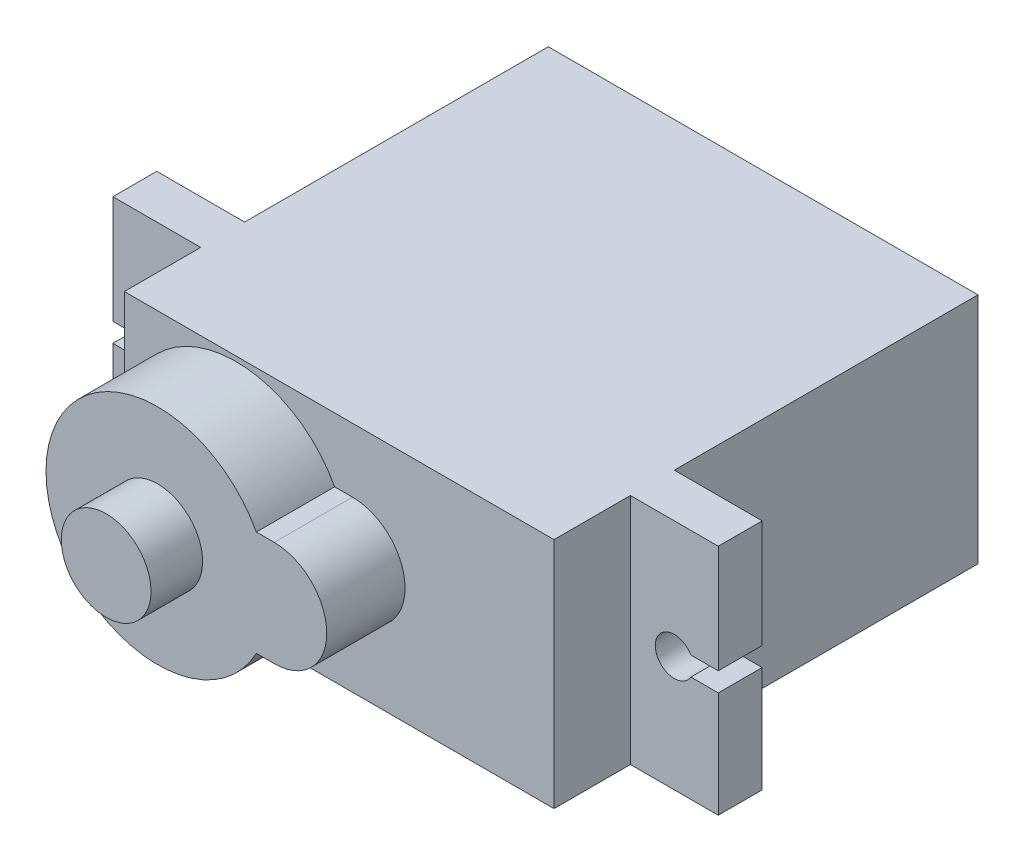
SolidWorks part; units mm, degrees
note: '?' marks a value the reader was unsure of.
ref_plane "Płaszczyzna przednia" through (0, 0, 0) normal (0, 0, 1) x (1, 0, 0)
ref_plane "Płaszczyzna górna" through (0, 0, 0) normal (0, 1, 0) x (1, 0, 0)
ref_plane "Płaszczyzna prawa" through (0, 0, 0) normal (1, 0, 0) x (0, 0, -1)
sketch "Szkic1" plane through (0, 0, 0) normal (0, 0, 1) x (1, 0, 0)
  line L1 (-22.7209, -0.2755) -> (-0.2209, -0.2755)
  line L2 (-22.7209, -0.2755) -> (-22.7209, -12.4755)
  line L3 (-22.7209, -12.4755) -> (-0.2209, -12.4755)
  line L4 (-0.2209, -0.2755) -> (-0.2209, -12.4755)
  dimension "D1" = 22.5
  dimension "D2" = 12.2
  dimension "D3" = 0.2209
  dimension "D4" = 0.2755
extrude "Dodanie-wyciągnięcie1" add sketch "Szkic1" along normal blind 22.2
sketch "Szkic2" plane through (-0.2209, 0, 0) normal (1, 0, 0) x (0, 0, -1)
  line L1 (-18.2, -12.4755) -> (-15.9, -12.4755)
  line L2 (-18.2, -12.4755) -> (-18.2, -0.2755)
  line L3 (-18.2, -0.2755) -> (-15.9, -0.2755)
  line L4 (-15.9, -12.4755) -> (-15.9, -0.2755)
  line L6 (-22.2, -12.4755) -> (0, -12.4755) construction
  line L7 (-22.2, -0.2755) -> (0, -0.2755) construction
  dimension "D1" = 2.3
  dimension "D2" = 4
extrude "Dodanie-wyciągnięcie2" add sketch "Szkic2" along normal blind 4.6 and the other way offset from surface (27.1 mm away) 4.6 other way up to face at (-22.7209, -6.3755, 11.1)
sketch "Szkic3" plane through (0, 0, 22.2) normal (0, 0, 1) x (1, 0, 0)
  line L0 (-10.7709, -9.1255) -> (-11.7076, -9.1255)
  line L1 (-10.7709, -3.6255) -> (-11.7076, -3.6255)
  line L3 (-0.2209, -6.3755) -> (-22.7209, -6.3755) construction
  line L4 (-22.7209, -0.2755) -> (-22.7209, -12.4755) construction
  line L5 (-0.2209, -12.4755) -> (-0.2209, -0.2755) construction
  line L7 (-22.7209, -0.2755) -> (-22.7209, -12.4755) construction
  arc A0 (-11.7076, -3.6255) -> (-11.7076, -9.1255) centre (-16.8709, -6.3755) ccw
  arc A1 (-10.7709, -9.1255) -> (-10.7709, -3.6255) centre (-10.7709, -6.3755) ccw
  point P15 (-8.0209, -6.3755)
  dimension "D1" = 14.7
  dimension "D2" = 5.85
  dimension "D3" = 2.75
extrude "Dodanie-wyciągnięcie3" add sketch "Szkic3" along normal blind 4.1
sketch "Szkic8" plane through (0, 0, 26.3) normal (0, 0, 1) x (1, 0, 0)
  circle A0 centre (-16.8709, -6.3755) radius 2.35
  point P0 (-16.8709, -6.3755)
  dimension "D1" = 4.7
extrude "Dodanie-wyciągnięcie4" add sketch "Szkic8" along normal blind 2.7
sketch "Szkic10" plane through (0, 0, 18.2) normal (0, 0, 1) x (1, 0, 0)
  line L0 (-27.3209, -5.9255) -> (-27.3209, -6.9255)
  line L2 (-27.3209, -5.9255) -> (-25.8869, -5.9255)
  line L3 (-27.3209, -6.9255) -> (-25.8869, -6.9255)
  line L4 (-27.3209, -12.4755) -> (-27.3209, -0.2755) construction
  line L5 (-27.3209, -0.2755) -> (-22.7209, -0.2755) construction
  line L6 (-11.4709, -0.2755) -> (-11.4709, 6.8844) construction
  line L7 (-0.2209, -0.2755) -> (-22.7209, -0.2755) construction
  line L8 (-25.0209, -0.2755) -> (-25.0209, -11.2341) construction
  line L9 (4.3791, -6.9255) -> (2.9451, -6.9255)
  line L10 (4.3791, -5.9255) -> (2.9451, -5.9255)
  line L11 (4.3791, -5.9255) -> (4.3791, -6.9255)
  arc A0 (-25.8869, -6.9255) -> (-25.8869, -5.9255) centre (-25.0209, -6.4255) ccw
  arc A1 (2.9451, -6.9255) -> (2.9451, -5.9255) centre (2.0791, -6.4255) cw
  point P2 (-27.3209, -6.4255)
  point P10 (-27.3209, -6.3755)
  point P23 (4.3791, -6.3755)
  point P24 (4.3791, -6.4255)
  dimension "D1" = 1
  dimension "D4" = 5.65
extrude "Wytnij-wyciągnięcie2" cut sketch "Szkic10" against normal up to surface (2.3 mm away) up to face at (-25.0209, -6.3755, 15.9)
sketch "Szkic11" plane through (-0.2209, 0, 0) normal (1, 0, 0) x (0, 0, -1)
  line L0 (-5.2, -1.4509) -> (-5.2, -9.3943) construction
  line L3 (0, -6.3755) -> (-7.5789, -6.3755) construction
  line L4 (0, -12.4755) -> (0, -0.2755) construction
  circle A4 centre (-4.45, -6.3755) radius 0.75
  circle A5 centre (-4.45, -4.8255) radius 0.75
  circle A6 centre (-4.45, -7.9255) radius 0.75
  dimension "D1" = 1.5
  dimension "D2" = 1.5
  dimension "D3" = 1.5
  dimension "D4" = 5.2
  dimension "D5" = 1.55
  dimension "D6" = 1.55
extrude "Dodanie-wyciągnięcie8" add sketch "Szkic11" against normal offset from surface (25.5 mm away) 3 up to face at (-22.7209, -6.3755, 7.95) offset beyond the face yes
ref_axis "os serwa" through (-16.8709, -6.3755, 36.4528) along (0, 0, -1)?
sketch "Sketch1" plane through (0, 0, 0) normal (0, 1, 0) x (1, 0, 0)
  line L0 (-22.7209, -26.3) -> (-8.0209, -26.3) construction
  line L2 (-16.8709, -10.5369) -> (-16.8709, -26.3) construction
  line L26 (-22.7209, 0) -> (-22.7209, -15.9) construction
  line L27 (-22.7209, -15.9) -> (-27.3209, -15.9) construction
  line L28 (-27.3209, -15.9) -> (-27.3209, -18.2) construction
  line L29 (-27.3209, -18.2) -> (-22.7209, -18.2) construction
  line L30 (-22.7209, -18.2) -> (-22.7209, -22.2) construction
  line L31 (-22.7209, -22.2) -> (-0.2209, -22.2) construction
  line L32 (-0.2209, -22.2) -> (-0.2209, -18.2) construction
  line L33 (-0.2209, -18.2) -> (4.3791, -18.2) construction
  line L34 (4.3791, -18.2) -> (4.3791, -15.9) construction
  line L35 (4.3791, -15.9) -> (-0.2209, -15.9) construction
  line L36 (-0.2209, -15.9) -> (-0.2209, 0) construction
  line L37 (-0.2209, 0) -> (-22.7209, 0) construction
  dimension "D2" = 4.1
  dimension "D3" = 4.3791
  dimension "D4" = 0.2209
  dimension "D5" = 16.8709
  dimension "D1" = 5.85
  dimension "D6" = 15.9
  dimension "D7" = 18.2
  dimension "D8" = 22.2
